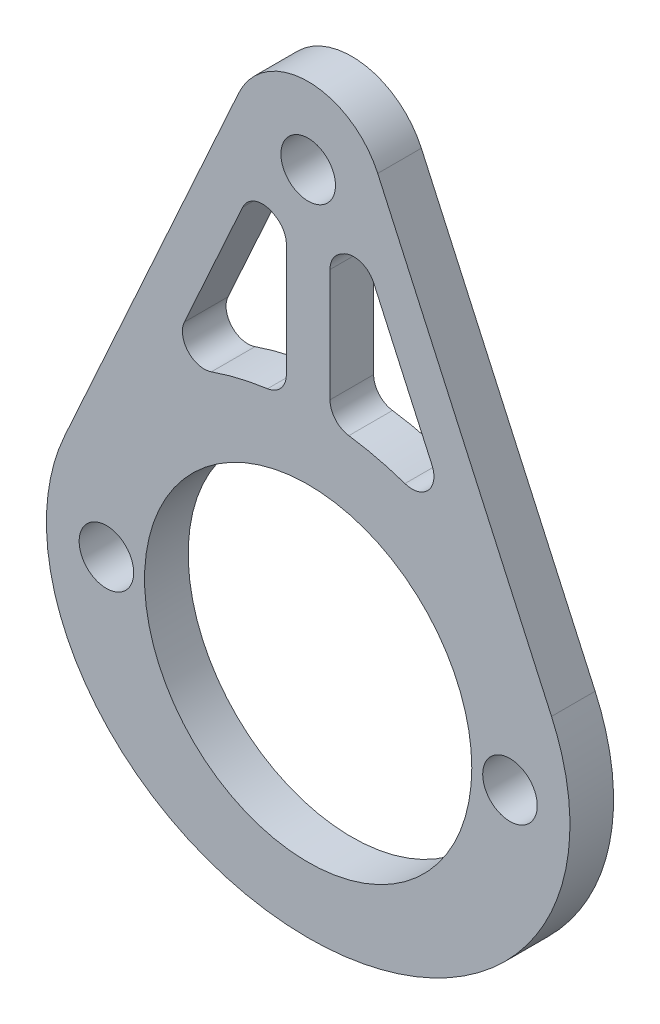
SolidWorks part; units mm, degrees
material "A2017"
ref_plane "正面" through (0, 0, 0) normal (0, 0, 1) x (1, 0, 0)
ref_plane "平面" through (0, 0, 0) normal (0, 1, 0) x (1, 0, 0)
ref_plane "右側面" through (0, 0, 0) normal (1, 0, 0) x (0, 0, -1)
sketch "ｽｹｯﾁ1" plane through (0, 0, 0) normal (0, 0, 1) x (1, 0, 0)
  line L0 (0, 0) -> (9.25, 0) construction
  line L1 (0, 0) -> (0, 7.5) construction
  line L2 (0, 0) -> (0, 20) construction
  line L3 (-11.1545, 3.8716) -> (-3.1877, 21.4451)
  line L4 (11.1545, 3.8716) -> (3.1877, 21.4451)
  circle A0 centre (0, 0) radius 7.5
  circle A1 centre (9.25, 0) radius 2.75 construction
  circle A2 centre (9.25, 0) radius 1
  circle A3 centre (0, 0) radius 10.5 construction
  circle A4 centre (-9.25, 0) radius 1
  circle A5 centre (0, 20) radius 3 construction
  arc A6 (3.1877, 21.4451) -> (-3.1877, 21.4451) centre (0, 20) ccw
  ellipse E0 centre (0, 0) end of major axis (12, 0) minor radius 10.5 (-11.1545, 3.8716) -> (11.1545, 3.8716) ccw
  dimension "D1" = 18.5
  dimension "D2" = 15
  dimension "D3" = 5.5
  dimension "D4" = 2
  dimension "D7" = 6
  dimension "D8" = 0.5
  dimension "D6" = 20
  dimension "D5" = 3
extrude "ﾎﾞｽ - 押し出し1" add sketch "ｽｹｯﾁ1" along normal blind 2
hole_wizard "M3 ねじ穴1" positions "ｽｹｯﾁ2" profile "ｽｹｯﾁ3" tap size "M3" standard "JIS" end condition through all
sketch "ｽｹｯﾁ2" plane through (0, 0, 0) normal (0, 0, -1) x (-1, 0, 0)
  point P0 (-9.25, 0)
  point P3 (9.25, 0)
sketch "ｽｹｯﾁ3" plane through (9.25, 0, 0) normal (1, 0, 0) x (0, 1, 0)
  line L0 (0, 0) -> (0, 2)
  line L1 (0, 2) -> (1.25, 2)
  line L2 (1.25, 2) -> (1.25, 0)
  line L5 (1.25, 0) -> (0, 0)
  line L11 (0, -6.35) -> (0, 107.95) construction
  dimension "次ｻｰﾌｪｽまでのねじ下穴ﾄﾞﾘﾙ直径" = 2.5
  dimension "次ｻｰﾌｪｽまでのねじ下穴ﾄﾞﾘﾙの深さ" = 2
cosmetic thread "穴のねじ山1" parameters "D2"=3
cosmetic thread "穴のねじ山2" parameters "D2"=3
sketch "ｽｹｯﾁ4" plane through (0, 0, 0) normal (0, 0, -1) x (-1, 0, 0)
  line L0 (0, 20) -> (0, 0) construction
  line L2 (1, 10.4635) -> (-1, 10.4635)
  line L3 (1, 10.4635) -> (1, 17.1716)
  line L4 (1, 17.1716) -> (-1, 17.1716)
  line L5 (-1, 10.4635) -> (-1, 17.1716)
  line L6 (1, 10.4635) -> (-1, 17.1716) construction
  line L7 (1, 17.1716) -> (-1, 10.4635) construction
  line L9 (1.3662, 20.6193) -> (9.3329, 3.0458)
  line L10 (1.3662, 20.6193) -> (9.3329, 3.0458)
  line L12 (-9.3329, 3.0458) -> (-1.3662, 20.6193)
  line L13 (-9.3329, 3.0458) -> (-1.3662, 20.6193)
  circle A2 centre (0, 20) radius 3
  ellipse E0 centre (0, 0) end of major axis (-12, 0) minor radius 10.5 (8.5484, -7.369) -> (-8.5484, -7.369) ccw construction
  ellipse E1 centre (0, 0) end of major axis (-12, 0) minor radius 10.5 (8.5484, -7.369) -> (-8.5484, -7.369) ccw
  point P18 (0, 13.8175)
  dimension "D4" = 6
  dimension "D1" = 2
  dimension "D2" = 2
  dimension "D3" = 2
extrude "ｶｯﾄ - 押し出し1" cut sketch "ｽｹｯﾁ4" against normal through all contours E1 L5 A2 L13 | E1 L10 A2 L3 region at (-3.0466, 13.0793, 0) region at (3.0466, 13.0793, 0)
fillet "ﾌｨﾚｯﾄ1" radius 1 8 edges at (-1, 17.1716, 1) (-2.4389, 18.2531, 1) (-6.7885, 8.6583, 1) (2.4389, 18.2531, 1) (1, 17.1716, 1) (1, 10.4635, 1) (6.7885, 8.6583, 1) (-1, 10.4635, 1)
hole_wizard "M3 ねじ穴2" positions "ｽｹｯﾁ5" profile "ｽｹｯﾁ6" tap size "M3" standard "JIS" end condition through all
sketch "ｽｹｯﾁ5" plane through (0, 0, 2) normal (0, 0, 1) x (1, 0, 0)
  point P0 (0, 20)
sketch "ｽｹｯﾁ6" plane through (0, 20, 2) normal (1, 0, 0) x (0, -1, 0)
  line L0 (0, 0) -> (0, 2)
  line L1 (0, 2) -> (1.25, 2)
  line L2 (1.25, 2) -> (1.25, 0)
  line L5 (1.25, 0) -> (0, 0)
  line L11 (0, -6.35) -> (0, 107.95) construction
  dimension "次ｻｰﾌｪｽまでのねじ下穴ﾄﾞﾘﾙ直径" = 2.5
  dimension "次ｻｰﾌｪｽまでのねじ下穴ﾄﾞﾘﾙの深さ" = 2
cosmetic thread "穴のねじ山3" parameters "D2"=3
